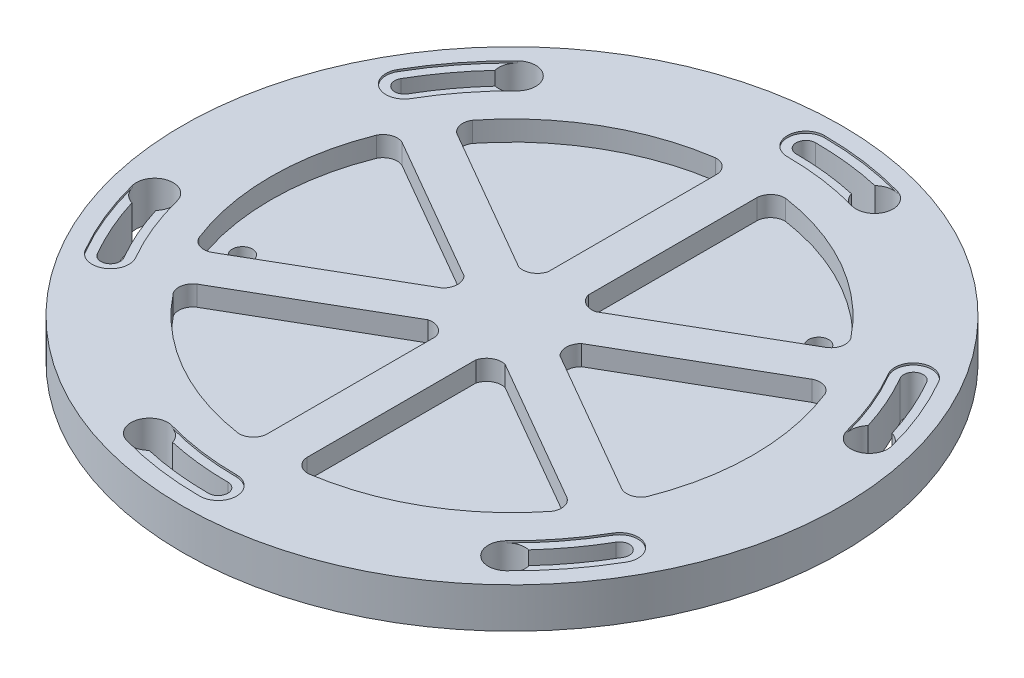
SolidWorks part; units mm, degrees
material "1060 Alloy"
ref_plane "Front Plane" through (0, 0, 0) normal (0, 0, 1) x (1, 0, 0)
ref_plane "Top Plane" through (0, 0, 0) normal (0, 1, 0) x (1, 0, 0)
ref_plane "Right Plane" through (0, 0, 0) normal (1, 0, 0) x (0, 0, -1)
sketch "Sketch1" plane through (0, 0, 0) normal (0, 1, 0) x (1, 0, 0)
  circle A0 centre (0, 0) radius 82
  arc A1 (0, 77.7102) -> (0, 68.5398) centre (0, 73.125) ccw
  arc A2 (0, 73.125) -> (19.8133, 70.3896) centre (0, 0) cw construction
  arc A3 (20.4672, 72.7124) -> (0, 75.5381) centre (0, 0) ccw construction
  arc A4 (19.1595, 68.0668) -> (0, 70.7119) centre (0, 0) ccw construction
  arc A5 (19.1595, 68.0668) -> (20.4672, 72.7124) centre (19.8133, 70.3896) ccw construction
  arc A6 (0, 75.5381) -> (0, 70.7119) centre (0, 73.125) ccw construction
  arc A7 (0, 73.125) -> (19.8133, 70.3896) centre (0, 0) cw construction
  arc A8 (21.0557, 74.8033) -> (0, 77.7102) centre (0, 0) ccw construction
  arc A9 (18.571, 65.9759) -> (0, 68.5398) centre (0, 0) ccw construction
  arc A10 (18.571, 65.9759) -> (21.0557, 74.8033) centre (19.8133, 70.3896) ccw construction
  arc A11 (0, 77.7102) -> (0, 68.5398) centre (0, 73.125) ccw construction
  arc A12 (15.4421, 69.0052) -> (16.6259, 73.6857) centre (19.8133, 70.3896) ccw
  arc A13 (0, 75.5381) -> (0, 70.7119) centre (0, 73.125) ccw
  arc A14 (0, 70.7119) -> (15.4421, 69.0052) centre (0, 0) cw
  arc A15 (0, 75.5381) -> (16.6259, 73.6857) centre (0, 0) cw
  arc A16 (0, 77.7102) -> (21.0557, 74.8033) centre (0, 0) cw
  arc A17 (0, 68.5398) -> (18.571, 65.9759) centre (0, 0) cw
  circle A18 centre (0, 0) radius 82
  arc A19 (67.299, 38.8551) -> (59.3572, 34.2699) centre (63.3281, 36.5625) ccw
  arc A20 (65.4179, 37.769) -> (61.2383, 35.356) centre (63.3281, 36.5625) ccw
  arc A21 (65.4179, 37.769) -> (72.1266, 22.4444) centre (0, 0) cw
  arc A22 (67.299, 38.8551) -> (75.3094, 19.1669) centre (0, 0) cw
  arc A23 (67.4813, 21.1293) -> (72.1266, 22.4444) centre (70.8659, 18.036) ccw
  arc A24 (61.2383, 35.356) -> (67.4813, 21.1293) centre (0, 0) cw
  arc A25 (59.3572, 34.2699) -> (66.4223, 16.905) centre (0, 0) cw
  circle A26 centre (0, 0) radius 82
  arc A27 (67.299, -38.8551) -> (59.3572, -34.2699) centre (63.3281, -36.5625) ccw
  arc A28 (65.4179, -37.769) -> (61.2383, -35.356) centre (63.3281, -36.5625) ccw
  arc A29 (65.4179, -37.769) -> (55.5007, -51.2413) centre (0, 0) cw
  arc A30 (67.299, -38.8551) -> (54.2537, -55.6364) centre (0, 0) cw
  arc A31 (52.0392, -47.8759) -> (55.5007, -51.2413) centre (51.0525, -52.3537) ccw
  arc A32 (61.2383, -35.356) -> (52.0392, -47.8759) centre (0, 0) cw
  arc A33 (59.3572, -34.2699) -> (47.8513, -49.0709) centre (0, 0) cw
  circle A34 centre (0, 0) radius 82
  arc A35 (0, -77.7102) -> (0, -68.5398) centre (0, -73.125) ccw
  arc A36 (0, -75.5381) -> (0, -70.7119) centre (0, -73.125) ccw
  arc A37 (0, -75.5381) -> (-16.6259, -73.6857) centre (0, 0) cw
  arc A38 (0, -77.7102) -> (-21.0557, -74.8033) centre (0, 0) cw
  arc A39 (-15.4421, -69.0052) -> (-16.6259, -73.6857) centre (-19.8133, -70.3896) ccw
  arc A40 (0, -70.7119) -> (-15.4421, -69.0052) centre (0, 0) cw
  arc A41 (0, -68.5398) -> (-18.571, -65.9759) centre (0, 0) cw
  circle A42 centre (0, 0) radius 82
  arc A43 (-67.299, -38.8551) -> (-59.3572, -34.2699) centre (-63.3281, -36.5625) ccw
  arc A44 (-65.4179, -37.769) -> (-61.2383, -35.356) centre (-63.3281, -36.5625) ccw
  arc A45 (-65.4179, -37.769) -> (-72.1266, -22.4444) centre (0, 0) cw
  arc A46 (-67.299, -38.8551) -> (-75.3094, -19.1669) centre (0, 0) cw
  arc A47 (-67.4813, -21.1293) -> (-72.1266, -22.4444) centre (-70.8659, -18.036) ccw
  arc A48 (-61.2383, -35.356) -> (-67.4813, -21.1293) centre (0, 0) cw
  arc A49 (-59.3572, -34.2699) -> (-66.4223, -16.905) centre (0, 0) cw
  circle A50 centre (0, 0) radius 82
  arc A51 (-67.299, 38.8551) -> (-59.3572, 34.2699) centre (-63.3281, 36.5625) ccw
  arc A52 (-65.4179, 37.769) -> (-61.2383, 35.356) centre (-63.3281, 36.5625) ccw
  arc A53 (-65.4179, 37.769) -> (-55.5007, 51.2413) centre (0, 0) cw
  arc A54 (-67.299, 38.8551) -> (-54.2537, 55.6364) centre (0, 0) cw
  arc A55 (-52.0392, 47.8759) -> (-55.5007, 51.2413) centre (-51.0525, 52.3537) ccw
  arc A56 (-61.2383, 35.356) -> (-52.0392, 47.8759) centre (0, 0) cw
  arc A57 (-59.3572, 34.2699) -> (-47.8513, 49.0709) centre (0, 0) cw
  point P7 (10.0006, 72.4379)
  point P15 (10.0006, 72.4379)
  point P111 (0, 0)
  dimension "D1" = 6
extrude "Boss-Extrude1" add sketch "Sketch1" along normal blind 10 contours A0 A57 A51 A54 A55 A49 A43 A46 A47 A41 A35 A38 A39 A33 A27 A30 A31 A25 A19 A22 A23 A17 A1 A16 A12 region at (0, 0, 0)
extrude "Boss-Extrude3" add sketch "Sketch1<4>" along normal blind 9.525 contours A43 A49 A47 A48 A44 A45 A46 region at (-71.7086, 0, 29.1755)
sketch "Sketch1<4>" plane through (0, 0, 0) normal (0, 1, 0) x (1, 0, 0) same geometry as "Sketch1"
pattern_circular "CirPattern1" count 6 over 360 about axis through (0, 10, 0) along (0, 1, 0) of "Boss-Extrude3"
sketch "Sketch2" plane through (0, 10, 0) normal (0, 1, 0) x (1, 0, 0)
  line L0 (-28.4808, 10.6699) -> (-51.0159, 23.6805)
  line L1 (-28.4808, 10.6699) -> (-14.6202, 2.6675)
  line L2 (-14.6202, -2.6675) -> (-28.4808, -10.6699)
  line L3 (-28.4808, -10.6699) -> (-51.0159, -23.6805)
  line L4 (-5, 30) -> (-5, 56.0213)
  line L5 (-5, 30) -> (-5, 13.9952)
  line L6 (-9.6202, 11.3277) -> (-23.4808, 19.3301)
  line L7 (-23.4808, 19.3301) -> (-46.0159, 32.3408)
  line L8 (-23.4808, -19.3301) -> (-9.6202, -11.3277)
  line L9 (-5, -13.9952) -> (-5, -30)
  line L10 (-23.4808, -19.3301) -> (-46.0159, -32.3408)
  line L11 (-5, -30) -> (-5, -56.0213)
  line L12 (23.4808, 19.3301) -> (46.0159, 32.3408)
  line L13 (23.4808, 19.3301) -> (9.6202, 11.3277)
  line L14 (5, 13.9952) -> (5, 30)
  line L15 (5, 30) -> (5, 56.0213)
  line L16 (28.4808, -10.6699) -> (51.0159, -23.6805)
  line L17 (28.4808, -10.6699) -> (14.6202, -2.6675)
  line L18 (14.6202, 2.6675) -> (28.4808, 10.6699)
  line L19 (28.4808, 10.6699) -> (51.0159, 23.6805)
  line L20 (5, -30) -> (5, -56.0213)
  line L21 (5, -30) -> (5, -13.9952)
  line L22 (9.6202, -11.3277) -> (23.4808, -19.3301)
  line L23 (23.4808, -19.3301) -> (46.0159, -32.3408)
  arc A0 (-47.034, -37.2532) -> (-8.7452, -59.3593) centre (0, 0) ccw
  arc A1 (-9.6202, -11.3277) -> (-5, -13.9952) centre (-8.6438, -14.9716) cw
  arc A2 (-47.034, -37.2532) -> (-8.7452, -59.3593) centre (0, 0) ccw
  arc A3 (-47.034, -37.2532) -> (-46.0159, -32.3408) centre (-44.0688, -35.3061) cw
  arc A4 (-5, -56.0213) -> (-8.7452, -59.3593) centre (-8.5416, -55.8177) cw
  arc A5 (-55.7792, 22.1061) -> (-51.0159, 23.6805) centre (-52.6103, 20.5116) cw
  arc A6 (-14.6202, 2.6675) -> (-14.6202, -2.6675) centre (-17.2877, 0) cw
  arc A7 (-51.0159, -23.6805) -> (-55.7792, -22.1061) centre (-52.6103, -20.5116) cw
  arc A8 (-47.034, -37.2532) -> (-8.7452, -59.3593) centre (0, 0) ccw
  arc A9 (-8.7452, 59.3593) -> (-5, 56.0213) centre (-8.5416, 55.8177) cw
  arc A10 (-5, 13.9952) -> (-9.6202, 11.3277) centre (-8.6438, 14.9716) cw
  arc A11 (-46.0159, 32.3408) -> (-47.034, 37.2532) centre (-44.0688, 35.3061) cw
  arc A12 (-47.034, -37.2532) -> (-8.7452, -59.3593) centre (0, 0) ccw
  arc A13 (47.034, 37.2532) -> (46.0159, 32.3408) centre (44.0688, 35.3061) cw
  arc A14 (9.6202, 11.3277) -> (5, 13.9952) centre (8.6438, 14.9716) cw
  arc A15 (5, 56.0213) -> (8.7452, 59.3593) centre (8.5416, 55.8177) cw
  arc A16 (-47.034, -37.2532) -> (-8.7452, -59.3593) centre (0, 0) ccw
  arc A17 (55.7792, -22.1061) -> (51.0159, -23.6805) centre (52.6103, -20.5116) cw
  arc A18 (14.6202, -2.6675) -> (14.6202, 2.6675) centre (17.2877, 0) cw
  arc A19 (51.0159, 23.6805) -> (55.7792, 22.1061) centre (52.6103, 20.5116) cw
  arc A20 (-47.034, -37.2532) -> (-8.7452, -59.3593) centre (0, 0) ccw
  arc A21 (8.7452, -59.3593) -> (5, -56.0213) centre (8.5416, -55.8177) cw
  arc A22 (5, -13.9952) -> (9.6202, -11.3277) centre (8.6438, -14.9716) cw
  arc A23 (46.0159, -32.3408) -> (47.034, -37.2532) centre (44.0688, -35.3061) cw
  arc A24 (8.7452, -59.3593) -> (47.034, -37.2532) centre (0, 0) ccw
  arc A25 (8.7452, -59.3593) -> (47.034, -37.2532) centre (0, 0) ccw
  arc A26 (8.7452, -59.3593) -> (47.034, -37.2532) centre (0, 0) ccw
  arc A27 (8.7452, -59.3593) -> (47.034, -37.2532) centre (0, 0) ccw
  arc A28 (8.7452, -59.3593) -> (47.034, -37.2532) centre (0, 0) ccw
  arc A29 (8.7452, -59.3593) -> (47.034, -37.2532) centre (0, 0) ccw
  arc A30 (-55.7792, 22.1061) -> (-55.7792, -22.1061) centre (0, 0) ccw
  arc A31 (-55.7792, 22.1061) -> (-55.7792, -22.1061) centre (0, 0) ccw
  arc A32 (-55.7792, 22.1061) -> (-55.7792, -22.1061) centre (0, 0) ccw
  arc A33 (-55.7792, 22.1061) -> (-55.7792, -22.1061) centre (0, 0) ccw
  arc A34 (-55.7792, 22.1061) -> (-55.7792, -22.1061) centre (0, 0) ccw
  arc A35 (-55.7792, 22.1061) -> (-55.7792, -22.1061) centre (0, 0) ccw
  arc A36 (-8.7452, 59.3593) -> (-47.034, 37.2532) centre (0, 0) ccw
  arc A37 (-8.7452, 59.3593) -> (-47.034, 37.2532) centre (0, 0) ccw
  arc A38 (-8.7452, 59.3593) -> (-47.034, 37.2532) centre (0, 0) ccw
  arc A39 (-8.7452, 59.3593) -> (-47.034, 37.2532) centre (0, 0) ccw
  arc A40 (-8.7452, 59.3593) -> (-47.034, 37.2532) centre (0, 0) ccw
  arc A41 (-8.7452, 59.3593) -> (-47.034, 37.2532) centre (0, 0) ccw
  arc A42 (47.034, 37.2532) -> (8.7452, 59.3593) centre (0, 0) ccw
  arc A43 (47.034, 37.2532) -> (8.7452, 59.3593) centre (0, 0) ccw
  arc A44 (47.034, 37.2532) -> (8.7452, 59.3593) centre (0, 0) ccw
  arc A45 (47.034, 37.2532) -> (8.7452, 59.3593) centre (0, 0) ccw
  arc A46 (47.034, 37.2532) -> (8.7452, 59.3593) centre (0, 0) ccw
  arc A47 (47.034, 37.2532) -> (8.7452, 59.3593) centre (0, 0) ccw
  arc A48 (55.7792, -22.1061) -> (55.7792, 22.1061) centre (0, 0) ccw
  arc A49 (55.7792, -22.1061) -> (55.7792, 22.1061) centre (0, 0) ccw
  arc A50 (55.7792, -22.1061) -> (55.7792, 22.1061) centre (0, 0) ccw
  arc A51 (55.7792, -22.1061) -> (55.7792, 22.1061) centre (0, 0) ccw
  arc A52 (55.7792, -22.1061) -> (55.7792, 22.1061) centre (0, 0) ccw
  arc A53 (55.7792, -22.1061) -> (55.7792, 22.1061) centre (0, 0) ccw
  point P83 (0, 0)
  dimension "D1" = 6
extrude "Cut-Extrude1" cut sketch "Sketch2" against normal blind 5 contours A5 A30 A7 L3 L2 A6 L1 L0 | A9 A36 A11 L7 L6 A10 L5 L4 | A13 A42 A15 L15 L14 A14 L13 L12 | A17 A48 A19 L19 L18 A18 L17 L16 | A21 A24 A23 L23 L22 A22 L21 L20 | A4 L11 L9 A1 L8 L10 A3 A0 region at (-42.1694, 10, 0) region at (-21.0847, 10, -36.5198) region at (-21.0847, 10, 36.5198) region at (21.0847, 10, -36.5198) region at (42.1694, 10, 0) region at (21.0847, 10, 36.5198)
sketch "Sketch3" plane through (0, 0, 0) normal (0, -1, 0) x (1, 0, 0)
  circle A0 centre (0, 0) radius 67.5
  circle A1 centre (-51.6852, 15.404) radius 2.5
  circle A2 centre (39.5145, -36.7824) radius 2.5
  dimension "D1" = 105.0752
extrude "Cut-Extrude2" cut sketch "Sketch3" against normal blind 5 contours A1
extrude "Cut-Extrude3" cut sketch "Sketch3<3>" against normal blind 5 contours A2
sketch "Sketch3<3>" plane through (0, 0, 0) normal (0, -1, 0) x (1, 0, 0) same geometry as "Sketch3"
